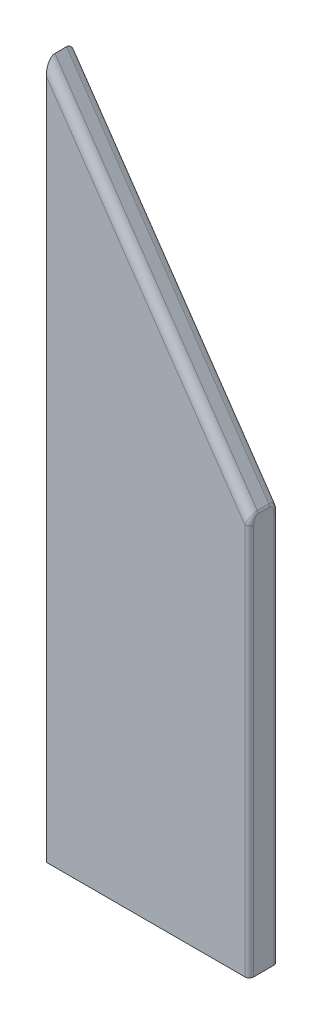
SolidWorks part; units mm, degrees
ref_plane "Front Plane" through (0, 0, 0) normal (0, 0, 1) x (1, 0, 0)
ref_plane "Top Plane" through (0, 0, 0) normal (0, 1, 0) x (1, 0, 0)
ref_plane "Right Plane" through (0, 0, 0) normal (1, 0, 0) x (0, 0, -1)
sketch "Sketch1" plane through (0, 0, 0) normal (0, 0, 1) x (1, 0, 0)
  line L0 (0, 0) -> (177.8, 0)
  line L1 (0, 0) -> (0, 609.6)
  line L2 (177.8, 0) -> (177.8, 350.52)
  line L3 (177.8, 350.52) -> (0, 609.6)
extrude "Boss-Extrude1" add sketch "Sketch1" along normal blind 25.4
fillet "Fillet1" radius 7.62 1 edges at (88.9, 480.06, 25.4)
fillet "Fillet2" radius 7.62 1 edges at (88.9, 480.06, 0)
fillet "Fillet3" radius 3.81 5 edges at (177.8, 168.5267, 0) (177.8, 346.5757, 2.2318) (177.8, 350.52, 12.7) (177.8, 346.5757, 23.1682) (177.8, 168.5267, 25.4)
